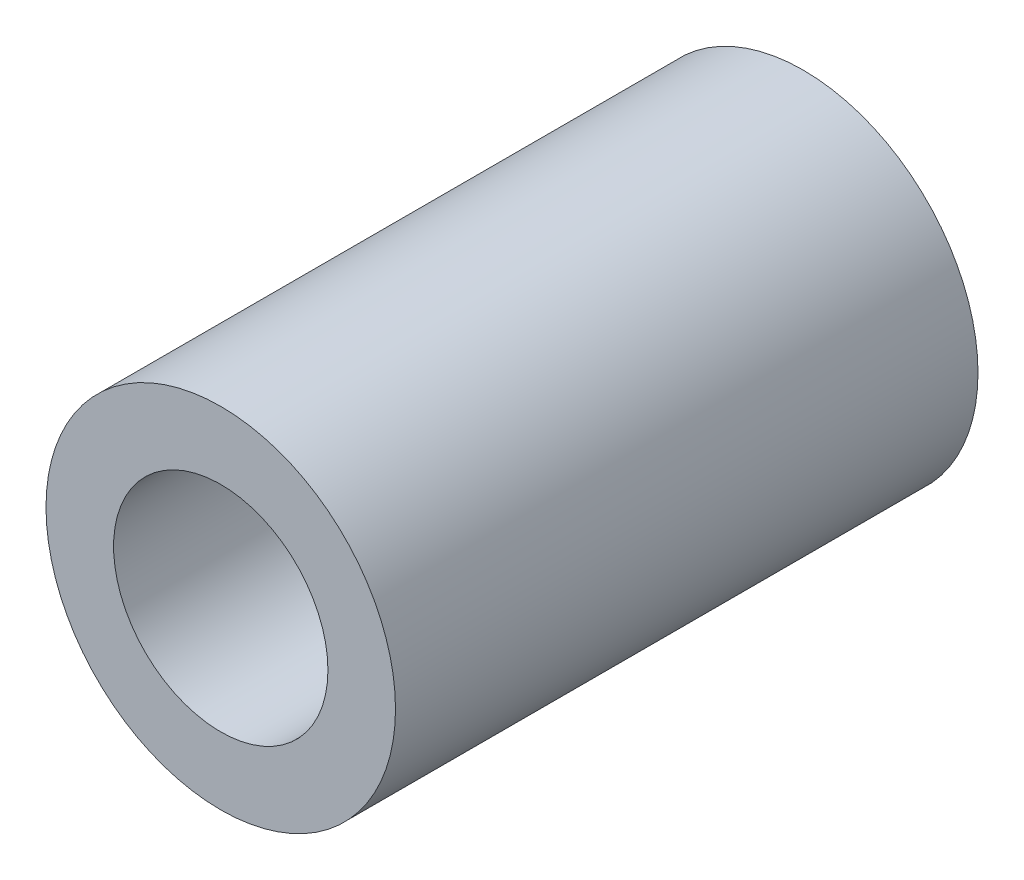
SolidWorks part; units mm, degrees
material "Nylon 6/10"
ref_plane "Front Plane" through (0, 0, 0) normal (0, 0, 1) x (1, 0, 0)
ref_plane "Top Plane" through (0, 0, 0) normal (0, 1, 0) x (1, 0, 0)
ref_plane "Right Plane" through (0, 0, 0) normal (1, 0, 0) x (0, 0, -1)
sketch "Sketch1" plane through (0, 0, 0) normal (0, 0, 1) x (1, 0, 0)
  circle A0 centre (0, 0) radius 2.3813
  circle A1 centre (0, 0) radius 1.4605
  dimension "OD" = 4.7625
  dimension "ID" = 2.921
extrude "Extrude1" add sketch "Sketch1" along normal mid plane 7.9375
sketch "Sketch2" plane through (0, 0, 0) normal (1, 0, 0) x (0, 0, -1)
  line L0 (-3.9688, -1.4605) -> (3.9688, -1.4605) construction
  line L3 (3.9688, 1.4605) -> (-3.9688, 1.4605) construction
  line L5 (-3.9688, -1.4605) -> (3.9688, -1.4605)
  line L6 (3.9688, 1.4605) -> (-3.9688, 1.4605)
sketch "Sketch4" plane through (0, 0, 3.9688) normal (0, 0, 1) x (1, 0, 0)
  line L0 (0, 0) -> (-1.0327, 1.0327)
  line L1 (0, -2.6194) -> (0, 2.6194) construction
  circle A0 centre (0, 0) radius 1.4605 construction
  dimension "D1" = 45
